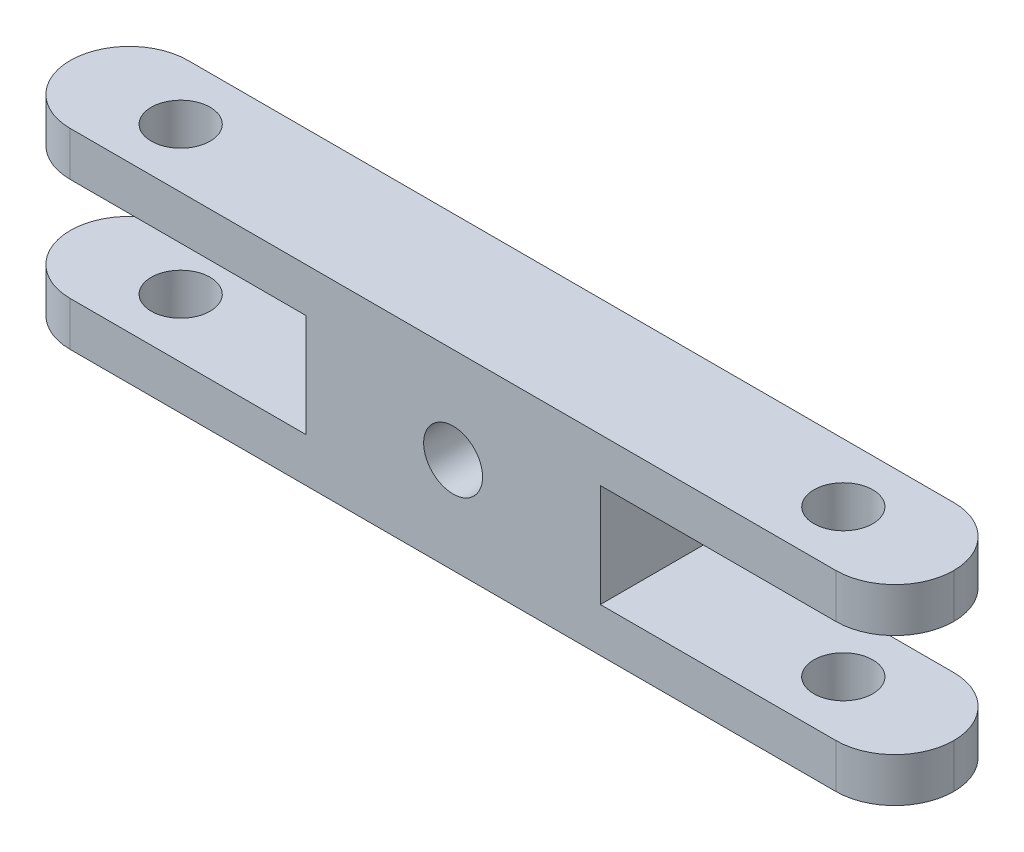
SolidWorks part; units mm, degrees
ref_plane "Front Plane" through (0, 0, 0) normal (0, 0, 1) x (1, 0, 0)
ref_plane "Top Plane" through (0, 0, 0) normal (0, 1, 0) x (1, 0, 0)
ref_plane "Right Plane" through (0, 0, 0) normal (1, 0, 0) x (0, 0, -1)
sketch "Sketch1" plane through (0, 0, 0) normal (0, 0, 1) x (1, 0, 0)
  line L1 (-30, 6.5) -> (30, 6.5)
  line L2 (-30, 6.5) -> (-30, -6.5)
  line L3 (-30, -6.5) -> (30, -6.5)
  line L4 (30, 6.5) -> (30, -6.5)
  line L5 (-30, 6.5) -> (30, -6.5) construction
  line L6 (-30, -6.5) -> (30, 6.5) construction
  point P0 (0, 0)
  dimension "D1" = 60
  dimension "D2" = 13
extrude "Boss-Extrude1" add sketch "Sketch1" along normal blind 8
fillet "Fillet1" radius 4 4 edges at (-30, 0, 0) (30, 0, 0) (30, 0, 8) (-30, 0, 8)
sketch "Sketch2" plane through (0, 0, 8) normal (0, 0, 1) x (1, 0, 0)
  line L1 (-30, 3.5) -> (-10, 3.5)
  line L2 (-30, 3.5) -> (-30, -3.5)
  line L3 (-30, -3.5) -> (-10, -3.5)
  line L4 (30, 3.5) -> (30, -3.5)
  line L5 (-30, 3.5) -> (-10, 1.1667) construction
  line L6 (-30, -3.5) -> (-10, -1.1667) construction
  line L7 (-10, 3.5) -> (-10, -3.5)
  line L8 (10, -3.5) -> (10, 3.5)
  line L9 (10, -3.5) -> (30, -3.5)
  line L10 (10, 1.1667) -> (30, 3.5) construction
  line L11 (10, -1.1667) -> (30, -3.5) construction
  line L12 (10, 3.5) -> (30, 3.5)
  point P0 (0, 0)
  dimension "D1" = 7
  dimension "D2" = 20
  dimension "D3" = 20
  dimension "D4" = 20
extrude "Cut-Extrude1" cut sketch "Sketch2" against normal through all
sketch "Sketch3" plane through (0, 6.5, 0) normal (0, 1, 0) x (1, 0, 0)
  line L0 (-22.5, -4) -> (22.5, -4) construction
  line L1 (0, -4) -> (0, 0) construction
  circle A0 centre (-22.5, -4) radius 2
  circle A1 centre (22.5, -4) radius 2
  point P7 (-2.8736, -5.1755)
  dimension "D3" = 4
  dimension "D4" = 4
  dimension "D1" = 4
  dimension "D2" = 45
extrude "Cut-Extrude2" cut sketch "Sketch3" against normal through all
sketch "Sketch4" plane through (0, 0, 8) normal (0, 0, 1) x (1, 0, 0)
  circle A0 centre (0, 0) radius 2
extrude "Cut-Extrude3" cut sketch "Sketch4" against normal through all
